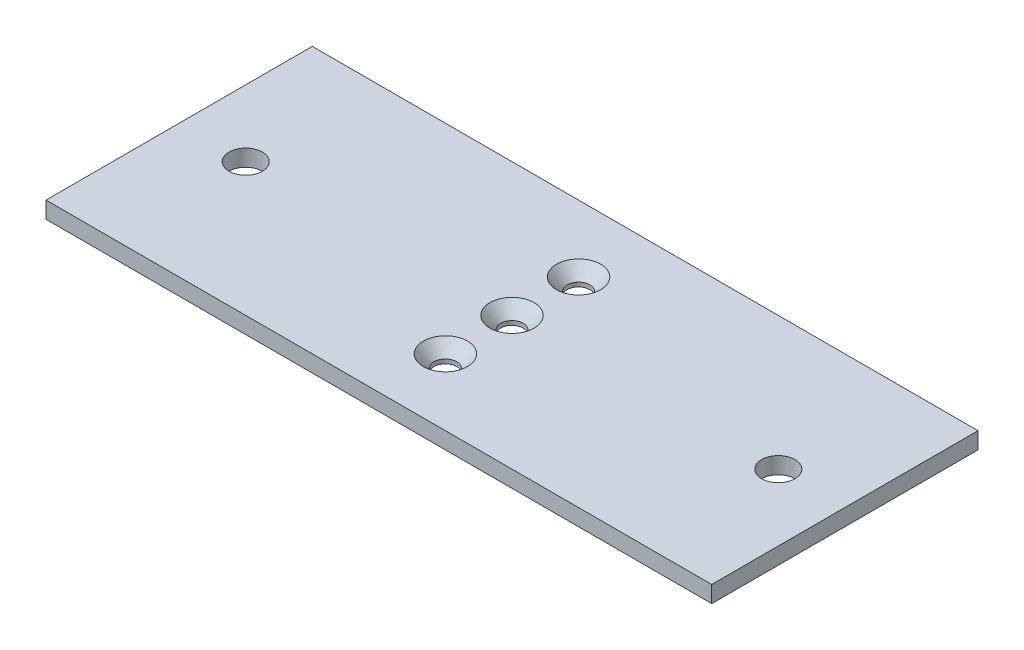
SolidWorks part; units mm, degrees
material "6061 Alloy"
ref_plane "Front Plane" through (0, 0, 0) normal (0, 0, 1) x (1, 0, 0)
ref_plane "Top Plane" through (0, 0, 0) normal (0, 1, 0) x (1, 0, 0)
ref_plane "Right Plane" through (0, 0, 0) normal (1, 0, 0) x (0, 0, -1)
sketch "Sketch1" plane through (0, 0, 0) normal (0, 1, 0) x (1, 0, 0)
  line L1 (0, 0) -> (127, 0)
  line L2 (0, 0) -> (0, 50.8)
  line L3 (0, 50.8) -> (127, 50.8)
  line L4 (127, 0) -> (127, 50.8)
  dimension "D1" = 127
  dimension "D2" = 50.8
extrude "Boss-Extrude1" add sketch "Sketch1" along normal blind 3.175
sketch "Sketch2" plane through (0, 3.175, 0) normal (0, 1, 0) x (1, 0, 0)
  line L0 (0, 0) -> (127, 0) construction
  line L1 (0, 50.8) -> (0, 0) construction
  circle A0 centre (12.7, 25.4) radius 3.175
  circle A1 centre (114.3, 25.4) radius 3.175
  dimension "D1" = 6.35
  dimension "D2" = 25.4
  dimension "D3" = 25.4
  dimension "D4" = 12.7
  dimension "D5" = 114.3
extrude "Cut-Extrude1" cut sketch "Sketch2" against normal blind 6.35
sketch "Sketch3" plane through (0, 3.175, 0) normal (0, 1, 0) x (1, 0, 0)
  line L0 (0, 50.8) -> (0, 0) construction
  line L1 (0, 0) -> (127, 0) construction
  circle A0 centre (63.5, 38.1) radius 3.175
  circle A1 centre (63.5, 25.4) radius 3.175
  circle A2 centre (63.5, 12.7) radius 3.175
  dimension "D1" = 63.5
  dimension "D3" = 63.5
  dimension "D4" = 25.4
  dimension "D5" = 38.1
  dimension "D6" = 12.7
  dimension "D2" = 63.5
hole_wizard "CSK for #8 Flat Head Machine Screw1" positions "Sketch5" profile "Sketch4" countersink size "#8" standard "ANSI Inch" end condition through all
sketch "Sketch5" plane through (0, 3.175, 0) normal (0, 1, 0) x (1, 0, 0)
  point P0 (63.5, 12.7)
  point P3 (63.5, 25.4)
  point P6 (63.5, 38.1)
sketch "Sketch4" plane through (63.5, 3.175, -12.7) normal (1, 0, 0) x (0, 0, 1)
  line L0 (0, 0) -> (0, 3.175)
  line L1 (0, 3.175) -> (2.1526, 3.175)
  line L2 (2.1526, 3.175) -> (2.1526, 2.3741)
  line L3 (2.1526, 2.3741) -> (4.2164, 0)
  line L5 (4.2164, 0) -> (0, 0)
  line L6 (-2.1527, 2.3741) -> (-4.2164, 0) construction
  line L11 (0, -6.35) -> (0, 107.95) construction
  dimension "Thru Hole Dia." = 4.3053
  dimension "Thru Hole Depth" = 3.175
  dimension "Near C'Sink Dia." = 8.4328
  dimension "Near C'Sink Angle" = 82
